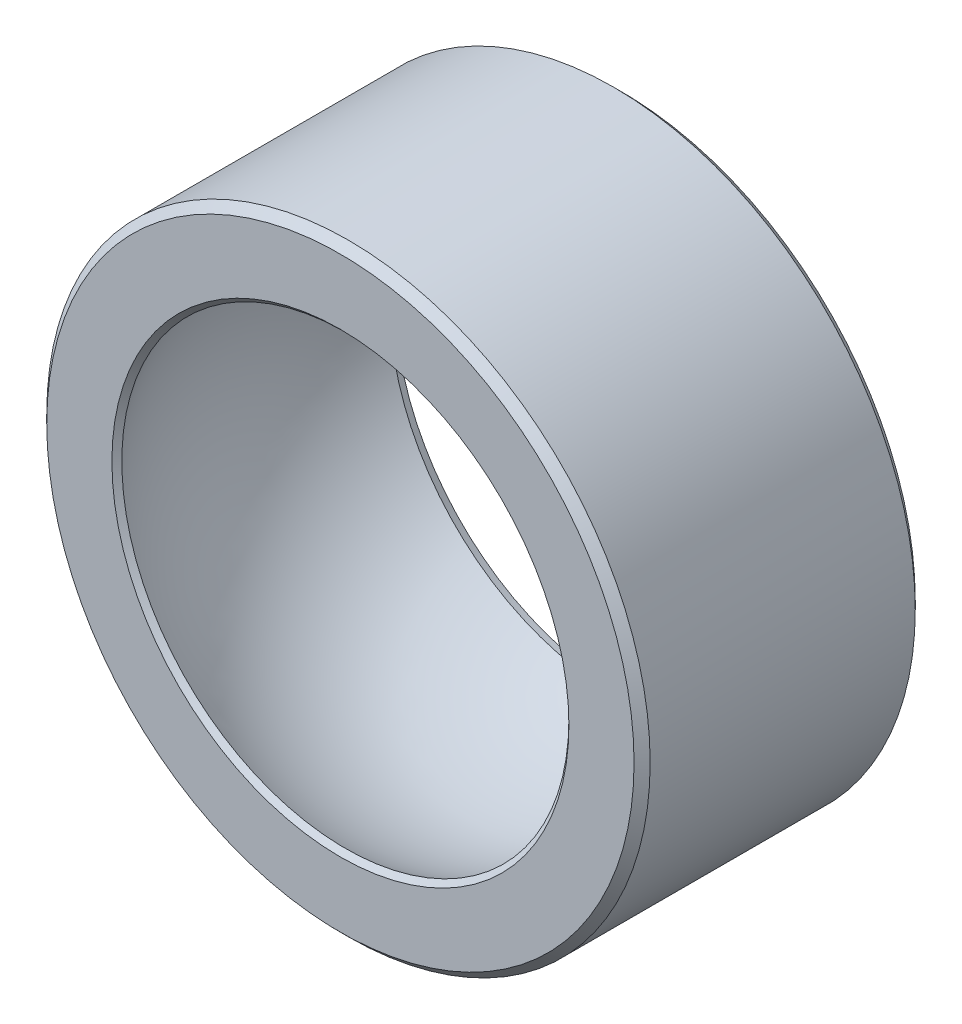
SolidWorks part; units mm, degrees
material "Ottone"
ref_plane "Piano frontale" through (0, 0, 0) normal (0, 0, 1) x (1, 0, 0)
ref_plane "Piano superiore" through (0, 0, 0) normal (0, 1, 0) x (1, 0, 0)
ref_plane "Piano destro" through (0, 0, 0) normal (1, 0, 0) x (0, 0, -1)
sketch "Schizzo1" plane through (0, 0, 0) normal (0, 0, 1) x (1, 0, 0)
  circle A0 centre (0, 0) radius 7.5
extrude "Estrusione1" add sketch "Schizzo1" along normal blind 3.495 and the other way blind 3.495
sketch "Schizzo2" plane through (0, 0, 0) normal (0, 1, 0) x (1, 0, 0)
  line L0 (0, 4.8154) -> (0, -4.6576) construction
  line L1 (0, 6.5) -> (0, -6.5)
  arc A0 (0, 6.5) -> (0, -6.5) centre (0, 0) ccw
revolve "Taglia-Rivoluzione1" cut sketch "Schizzo2" angle 360 about L0
chamfer "Smusso1" distance 0.2 angle 45 4 edges at (5.4804, 0, 3.495) (7.5, 0, 3.495) (5.4804, 0, -3.495) (7.5, 0, -3.495) first distance on face at (5.4804, 0, 3.495) first distance on face at (7.5, 0, 3.495) first distance on face at (5.4804, 0, -3.495)
